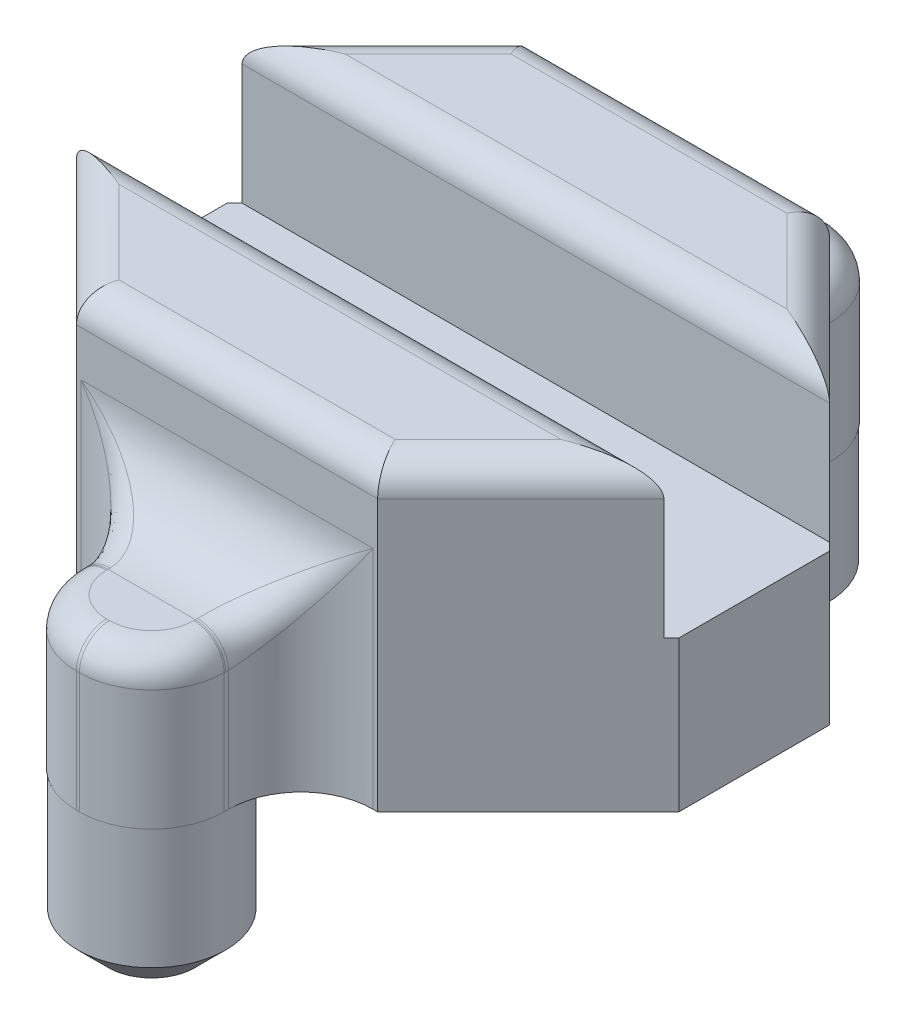
SolidWorks part; units mm, degrees
ref_plane "Front Plane" through (0, 0, 0) normal (0, 0, 1) x (1, 0, 0)
ref_plane "Top Plane" through (0, 0, 0) normal (0, 1, 0) x (1, 0, 0)
ref_plane "Right Plane" through (0, 0, 0) normal (1, 0, 0) x (0, 0, -1)
sketch "Sketch1" plane through (0, 0, 0) normal (0, 1, 0) x (1, 0, 0)
  line L1 (-12.7, -9.525) -> (12.7, -9.525)
  line L2 (-12.7, -9.525) -> (-12.7, 9.525)
  line L3 (-12.7, 9.525) -> (12.7, 9.525)
  line L4 (12.7, -9.525) -> (12.7, 9.525)
  line L5 (-12.7, -9.525) -> (12.7, 9.525) construction
  line L6 (-12.7, 9.525) -> (12.7, -9.525) construction
  point P0 (0, 0)
  dimension "D1" = 25.4
  dimension "D2" = 19.05
extrude "Boss-Extrude1" add sketch "Sketch1" along normal blind 12.7
sketch "Sketch2" plane through (0, 12.7, 0) normal (0, 1, 0) x (1, 0, 0)
  line L0 (12.7, -9.525) -> (12.7, 9.525) construction
  line L1 (-12.7, -3.4925) -> (12.7, -3.4925)
  line L2 (-12.7, -3.4925) -> (-12.7, 3.4925)
  line L3 (-12.7, 3.4925) -> (12.7, 3.4925)
  line L4 (12.7, -3.4925) -> (12.7, 3.4925)
  line L5 (-12.7, -3.4925) -> (12.7, 3.4925) construction
  line L6 (-12.7, 3.4925) -> (12.7, -3.4925) construction
  point P0 (0, 0)
  dimension "D1" = 6.985
extrude "Cut-Extrude1" cut sketch "Sketch2" against normal blind 6.35
sketch "Sketch3" plane through (0, 0, 0) normal (0, -1, 0) x (1, 0, 0)
  circle A0 centre (0, 12.7) radius 3.1115
  circle A1 centre (0, -12.7) radius 3.1115
  point P4 (0, 0)
  point P6 (-9.2687, 0)
  point P7 (0, 0)
  point P8 (-12.7, 0)
  point P9 (0, 0)
  point P10 (0.4361, -11.2194)
  point P11 (0.4361, 10.5454)
  point P13 (0, 0)
  dimension "D1" = 6.223
  dimension "D2" = 6.223
  dimension "D3" = 12.7
  dimension "D4" = 12.7
extrude "Boss-Extrude2" add sketch "Sketch3" along normal blind 6.35
sketch "Sketch4" plane through (0, 0, 0) normal (0, -1, 0) x (1, 0, 0)
  line L1 (-3.1115, -15.8115) -> (3.1115, -15.8115)
  line L2 (-3.1115, -15.8115) -> (-3.1115, 15.8115)
  line L3 (-3.1115, 15.8115) -> (3.1115, 15.8115)
  line L4 (3.1115, -15.8115) -> (3.1115, 15.8115)
  line L5 (-3.1115, -15.8115) -> (3.1115, 15.8115) construction
  line L6 (-3.1115, 15.8115) -> (3.1115, -15.8115) construction
  circle A0 centre (0, 12.7) radius 3.1115 construction
  point P0 (0, 0)
extrude "Boss-Extrude3" add sketch "Sketch4" against normal blind 6.35
chamfer "Chamfer1" distance 6.35 angle 45 4 edges at (12.7, 6.35, -9.525) (-12.7, 6.35, -9.525) (-12.7, 6.35, 9.525) (12.7, 6.35, 9.525)
fillet "Fillet1" radius 3.048 8 edges at (-3.1115, 3.175, 15.8115) (3.1115, 3.175, 15.8115) (3.1115, 3.175, 9.525) (-3.1115, 3.175, 9.525) (-3.1115, 3.175, -15.8115) (3.1115, 3.175, -15.8115) (3.1115, 3.175, -9.525) (-3.1115, 3.175, -9.525)
fillet "Fillet2" radius 1.27 8 edges at (-9.3662, 12.7, -6.5087) (0, 12.7, -9.525) (9.3662, 12.7, -6.5087) (0, 12.7, -3.4925) (9.3662, 12.7, 6.5088) (0, 12.7, 9.525) (-9.3662, 12.7, 6.5088) (0, 12.7, 3.4925)
fillet "Fillet3" radius 3.175 2 edges at (0, 6.35, 9.525) (0, 6.35, -9.525)
chamfer "Chamfer2" distance 1.27 angle 45 2 edges at (0, -6.35, 9.5885) (0, -6.35, -15.8115)
fillet "Fillet4" radius 1.27 18 edges at (3.5189, 6.812, -11.0507) (3.1115, 6.3506, -12.6365) (3.1115, 6.35, -12.7317) (2.2188, 6.35, -14.9188) (0, 6.35, -15.8115) (-3.5189, 6.812, -11.0507) (-3.1115, 6.3506, -12.6365) (-3.1115, 6.35, -12.7317) (3.5189, 6.812, 11.0507) (3.1115, 6.3506, 12.6365) (3.1115, 6.35, 12.7318) (2.2188, 6.35, 14.9188) (0, 6.35, 15.8115) (-2.2188, 6.35, 14.9188) (-3.1115, 6.35, 12.7318) (-3.1115, 6.3506, 12.6365) (-2.2188, 6.35, -14.9188) (-3.5189, 6.812, 11.0507)
